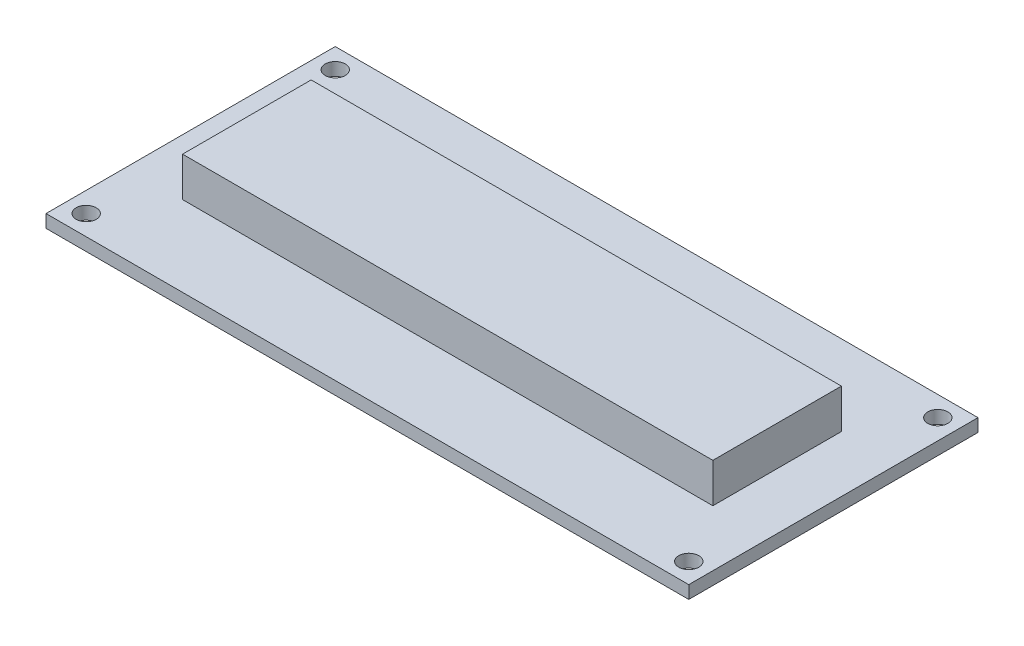
SolidWorks part; units mm, degrees
ref_plane "Front Plane" through (0, 0, 0) normal (0, 0, 1) x (1, 0, 0)
ref_plane "Top Plane" through (0, 0, 0) normal (0, 1, 0) x (1, 0, 0)
ref_plane "Right Plane" through (0, 0, 0) normal (1, 0, 0) x (0, 0, -1)
sketch "Sketch1" plane through (0, 0, 0) normal (0, 1, 0) x (1, 0, 0)
  line L1 (-40, 18) -> (40, 18)
  line L2 (-40, 18) -> (-40, -18)
  line L3 (-40, -18) -> (40, -18)
  line L4 (40, 18) -> (40, -18)
  line L5 (-40, 18) -> (40, -18) construction
  line L6 (-40, -18) -> (40, 18) construction
  point P0 (0, 0)
  dimension "D1" = 80
  dimension "D2" = 36
extrude "Boss-Extrude1" add sketch "Sketch1" along normal blind 1.6
sketch "Sketch3" plane through (0, 1.6, 0) normal (0, 1, 0) x (1, 0, 0)
  line L0 (40, 18) -> (-40, 18) construction
  line L1 (-33, 8) -> (33, 8)
  line L2 (-33, 8) -> (-33, -8)
  line L3 (-33, -8) -> (33, -8)
  line L4 (33, 8) -> (33, -8)
  line L5 (-33, 8) -> (33, -8) construction
  line L6 (-33, -8) -> (33, 8) construction
  line L8 (-40, 18) -> (-40, -18) construction
  point P0 (0, 0)
  dimension "D1" = 10
  dimension "D2" = 7
extrude "Boss-Extrude2" add sketch "Sketch3" along normal blind 4.9
sketch "Sketch4" plane through (0, 1.6, 0) normal (0, 1, 0) x (1, 0, 0)
  line L0 (40, 18) -> (-40, 18) construction
  line L1 (-40, 18) -> (-40, -18) construction
  circle A0 centre (-37.5, 15.5) radius 1.25
  dimension "D1" = 2.5
  dimension "D2" = 2.5
  dimension "D3" = 2.5
extrude "Cut-Extrude1" cut sketch "Sketch4" against normal blind 4.9
sketch "Sketch5" plane through (0, 1.6, 0) normal (0, 1, 0) x (1, 0, 0)
  line L0 (0, 18) -> (0, -18) construction
  line L1 (40, 18) -> (-40, 18) construction
  line L2 (-40, -18) -> (40, -18) construction
  line L3 (-40, 18) -> (-40, -18) construction
  line L4 (-40, 0) -> (40, 0) construction
  line L5 (40, -18) -> (40, 18) construction
ref_plane "Plane1" through (0, 0, 0) normal (-1, 0, 0) x (0, 0, 1)
mirror "Mirror2" about plane through (0, 0, 0) normal (-1, 0, 0) of "Cut-Extrude1"
ref_plane "Plane2" through (0, 0, 0) normal (0, 0, 1) x (1, 0, 0)
mirror "Mirror3" about plane through (0, 0, 0) normal (0, 0, 1) of "Mirror2", "Cut-Extrude1"
